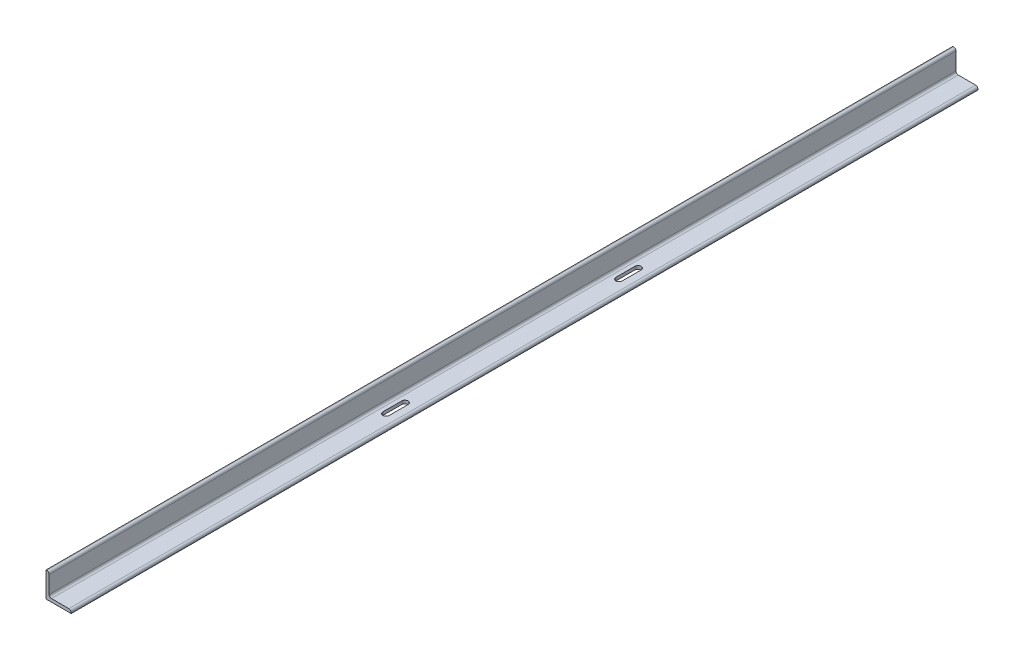
SolidWorks part; units mm, degrees
ref_plane "Front Plane" through (0, 0, 0) normal (0, 0, 1) x (1, 0, 0)
ref_plane "Top Plane" through (0, 0, 0) normal (0, 1, 0) x (1, 0, 0)
ref_plane "Right Plane" through (0, 0, 0) normal (1, 0, 0) x (0, 0, -1)
sketch "Sketch1" plane through (0, 0, 0) normal (0, 0, 1) x (1, 0, 0)
  line L0 (0, 0) -> (0, 50.8)
  line L1 (0, 50.8) -> (1.5926, 50.8)
  line L2 (6.35, 46.0426) -> (6.35, 11.1125)
  line L3 (11.1125, 6.35) -> (46.0426, 6.35)
  line L4 (50.8, 1.5926) -> (50.8, 0)
  line L5 (50.8, 0) -> (0, 0)
  arc A0 (50.8, 1.5926) -> (46.0426, 6.35) centre (46.0426, 1.5926) ccw
  arc A1 (1.5926, 50.8) -> (6.35, 46.0426) centre (1.5926, 46.0426) cw
  arc A2 (11.1125, 6.35) -> (6.35, 11.1125) centre (11.1125, 11.1125) cw
  circle A3 centre (0, 0) radius 4.7625 construction
  dimension "D2" = 1.5926
  dimension "Radius_1" = 4.7625
  dimension "Radius_2" = 4.7625
  dimension "D1" = 6.35
  dimension "V_leg" = 50.8
  dimension "H_leg" = 50.8
  dimension "Thickness" = 6.35
  dimension "Flat_wid" = 1.5926
extrude "Boss-Extrude1" add sketch "Sketch1" along normal mid plane 1828.8
sketch "Sketch5" plane through (0, 0, 0) normal (0, -1, 0) x (1, 0, 0)
  line L0 (25.4, -254) -> (25.4, -215.9) construction
  line L1 (19.05, -254) -> (19.05, -215.9)
  line L2 (31.75, -254) -> (31.75, -215.9)
  line L3 (25.4, -914.4) -> (25.4, 914.4) construction
  line L6 (0, 0) -> (50.8, 0) construction
  line L7 (50.8, 914.4) -> (50.8, -914.4) construction
  line L8 (25.4, 254) -> (25.4, 215.9) construction
  line L9 (19.05, 254) -> (19.05, 215.9)
  line L10 (31.75, 254) -> (31.75, 215.9)
  line L11 (0, -914.4) -> (50.8, -914.4) construction
  line L12 (0, 914.4) -> (50.8, 914.4) construction
  arc A0 (19.05, -254) -> (31.75, -254) centre (25.4, -254) ccw
  arc A1 (31.75, -215.9) -> (19.05, -215.9) centre (25.4, -215.9) ccw
  arc A2 (19.05, 254) -> (31.75, 254) centre (25.4, 254) cw
  arc A3 (31.75, 215.9) -> (19.05, 215.9) centre (25.4, 215.9) cw
  point P2 (25.4, -234.95)
  point P20 (25.4, 234.95)
  dimension "D1" = 12.7
  dimension "D2" = 38.1
  dimension "D3" = 234.95
extrude "Cut-Extrude2" cut sketch "Sketch5" against normal up to next
